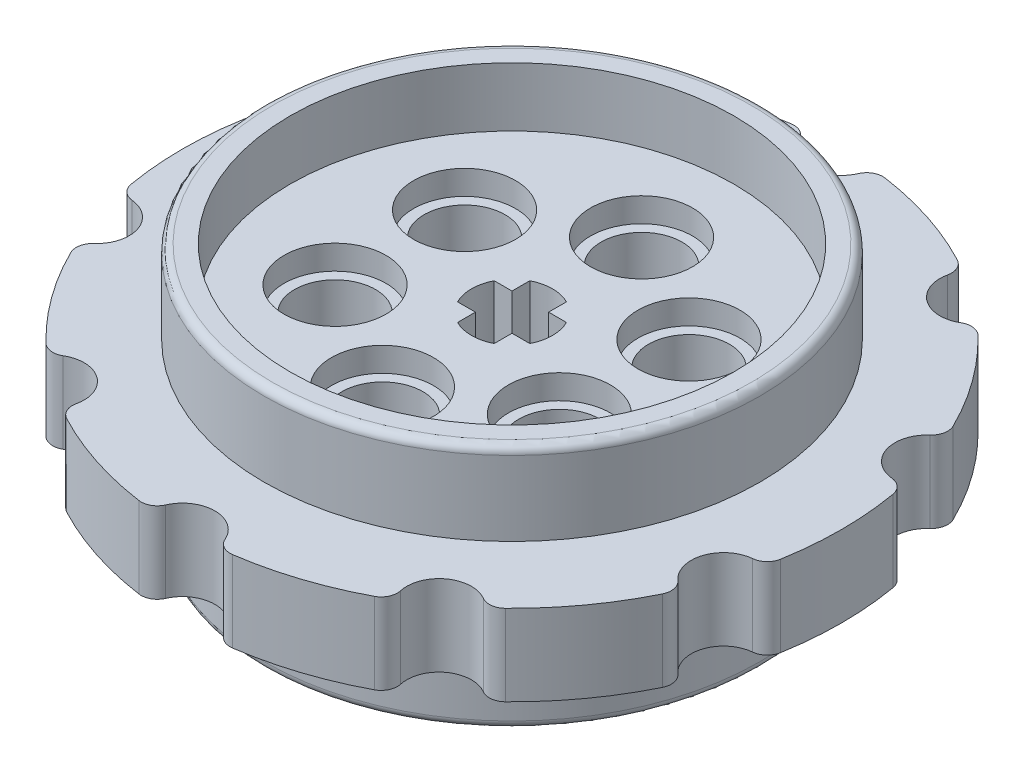
SolidWorks part; units mm, degrees
ref_plane "前视基准面" through (0, 0, 0) normal (0, 0, 1) x (1, 0, 0)
ref_plane "上视基准面" through (0, 0, 0) normal (0, 1, 0) x (1, 0, 0)
ref_plane "右视基准面" through (0, 0, 0) normal (1, 0, 0) x (0, 0, -1)
other "Configuration Table"
sketch "草图1" plane through (0, 0, 0) normal (0, 1, 0) x (1, 0, 0)
  circle A0 centre (0, 0) radius 15.3
  circle A1 centre (0, 0) radius 20.35
  circle A2 centre (0, 0) radius 13.7
  circle A3 centre (0, 20.35) radius 2
  dimension "D1" = 30.6
  dimension "D2" = 40.7
  dimension "D3" = 1.6
  dimension "D4" = 4
extrude "凸台-拉伸1" add sketch "草图1" along normal mid plane 15.2 contours A0 | A2
extrude "凸台-拉伸2" add sketch "草图1<3>" along normal mid plane 5 contours A1
sketch "草图1<3>" plane through (0, 0, 0) normal (0, 1, 0) x (1, 0, 0) same geometry as "草图1"
extrude "凸台-拉伸3" add sketch "草图1<7>" along normal mid plane 7.9 contours A2
sketch "草图1<7>" plane through (0, 0, 0) normal (0, 1, 0) x (1, 0, 0) same geometry as "草图1"
extrude "切除-拉伸1" cut sketch "草图1<4>" against normal through all both and the other way through all contours A3
sketch "草图1<4>" plane through (0, 0, 0) normal (0, 1, 0) x (1, 0, 0) same geometry as "草图1"
fillet "圆角1" radius 1 2 edges at (1.9976, 0, -20.2517) (-1.9976, 0, -20.2517)
pattern_circular "阵列(圆周)1" count 10 over 360 about axis through (0, 2.5, 0) along (0, -1, 0) of "切除-拉伸1", "圆角1"
fillet "圆角2" radius 0.5 2 edges at (0, -7.6, 15.3) (0, 7.6, 15.3)
sketch "草图2" plane through (0, 2.5, 0) normal (0, 1, 0) x (1, 0, 0)
  line L1 (-1.13, -2.23) -> (1.13, -2.23)
  line L2 (-1.13, -2.23) -> (-1.13, 2.23)
  line L3 (-1.13, 2.23) -> (1.13, 2.23)
  line L4 (1.13, -2.23) -> (1.13, 2.23)
  line L5 (-1.13, -2.23) -> (1.13, 2.23) construction
  line L6 (-1.13, 2.23) -> (1.13, -2.23) construction
  line L7 (-2.23, -1.13) -> (2.23, -1.13)
  line L8 (-2.23, -1.13) -> (-2.23, 1.13)
  line L9 (-2.23, 1.13) -> (2.23, 1.13)
  line L10 (2.23, -1.13) -> (2.23, 1.13)
  line L11 (-2.23, -1.13) -> (2.23, 1.13) construction
  line L12 (-2.23, 1.13) -> (2.23, -1.13) construction
  circle A0 centre (0, 0) radius 3.7
  circle A1 centre (0, 0) radius 3.15
  circle A2 centre (0, 0) radius 2.5
  dimension "D1" = 7.4
  dimension "D2" = 6.3
  dimension "D3" = 5
  dimension "D4" = 1.1
extrude "切除-拉伸2" cut sketch "草图2" against normal through all both and the other way through all contours L3 A2 | L8 A2 | L1 A2 | L10 A2 | L3 L4 L1 L2 | L9 L10 L7 L8 region at (0, 2.5, 2.3385) region at (-2.3385, 2.5, 0) region at (2.3385, 2.5, 0) region at (0, 2.5, -2.3385)
sketch "草图3" plane through (0, 2.5, 0) normal (0, 1, 0) x (1, 0, 0)
  circle A0 centre (0, 8) radius 3.7
  circle A1 centre (0, 8) radius 3.15
  circle A2 centre (0, 8) radius 2.5
  dimension "D1" = 7.4
  dimension "D3" = 6.3
  dimension "D4" = 5
  dimension "D2" = 8
extrude "切除-拉伸3" cut sketch "草图3" against normal through all both and the other way through all contours A2
extrude "切除-拉伸4" cut sketch "草图3<3>" against normal blind 1.5 from surface contours A1 starting at face at (0, 3.95, -5.5)
sketch "草图3<3>" plane through (0, 2.5, 0) normal (0, 1, 0) x (1, 0, 0) same geometry as "草图3"
extrude "切除-拉伸5" cut sketch "草图3<4>" along normal blind 1.5 from surface contours A1 starting at face at (0, -3.95, -5.5)
sketch "草图3<4>" plane through (0, 2.5, 0) normal (0, 1, 0) x (1, 0, 0) same geometry as "草图3"
pattern_circular "阵列(圆周)2" count 6 over 360 about axis through (0, 2.5, 0) along (0, -1, 0) of "切除-拉伸5", "切除-拉伸4", "切除-拉伸3" reverse direction yes
